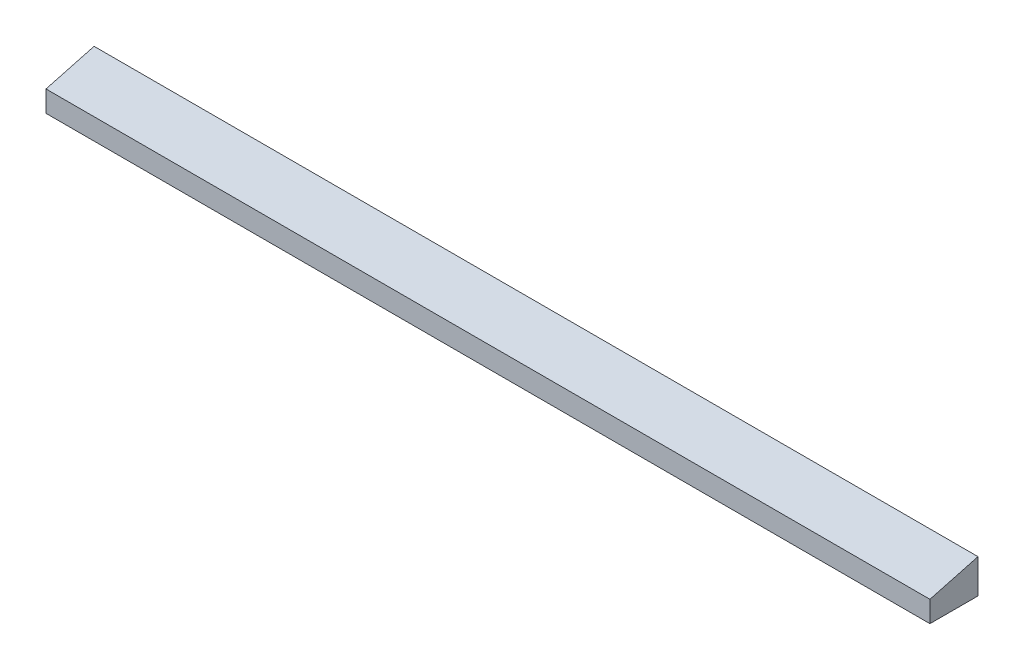
SolidWorks part; units mm, degrees
ref_plane "Alzado" through (0, 0, 0) normal (0, 0, 1) x (1, 0, 0)
ref_plane "Planta" through (0, 0, 0) normal (0, 1, 0) x (1, 0, 0)
ref_plane "Vista lateral" through (0, 0, 0) normal (1, 0, 0) x (0, 0, -1)
sketch "Croquis1" plane through (0, 0, 0) normal (0, 0, 1) x (1, 0, 0)
  line L1 (125, 5) -> (-125, 5)
  line L2 (125, 5) -> (125, -5)
  line L3 (125, -5) -> (-125, -5)
  line L4 (-125, 5) -> (-125, -5)
  line L5 (125, 5) -> (-125, -5) construction
  line L6 (125, -5) -> (-125, 5) construction
  point P0 (0, 0)
  dimension "D1" = 250
  dimension "D2" = 10
extrude "Saliente-Extruir1" add sketch "Croquis1" along normal blind 13.6
chamfer "Chaflán1" distance 15 angle 15 1 edges at (0, 5, 13.6) first distance on face at (0, 5, 6.8)
